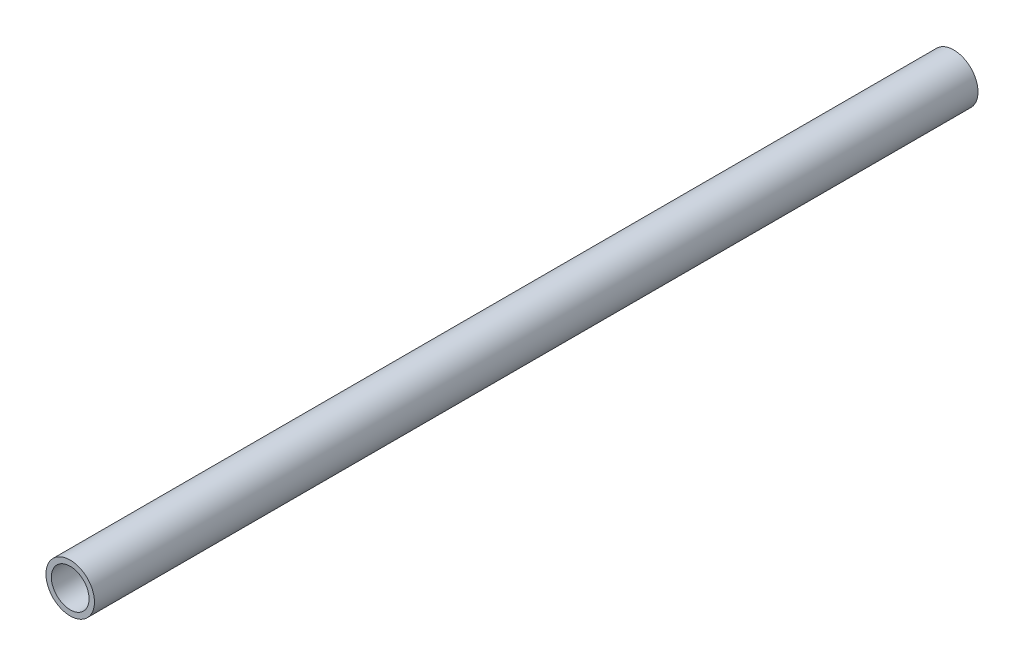
SolidWorks part; units mm, degrees
ref_plane "Front Plane" through (0, 0, 0) normal (0, 0, 1) x (1, 0, 0)
ref_plane "Top Plane" through (0, 0, 0) normal (0, 1, 0) x (1, 0, 0)
ref_plane "Right Plane" through (0, 0, 0) normal (1, 0, 0) x (0, 0, -1)
sketch "Sketch1" plane through (0, 0, 0) normal (0, 0, 1) x (1, 0, 0)
  circle A0 centre (0, 0) radius 9
  circle A1 centre (0, 0) radius 7
  dimension "D1" = 14
  dimension "D2" = 18
extrude "Boss-Extrude1" add sketch "Sketch1" along normal blind 327.978
